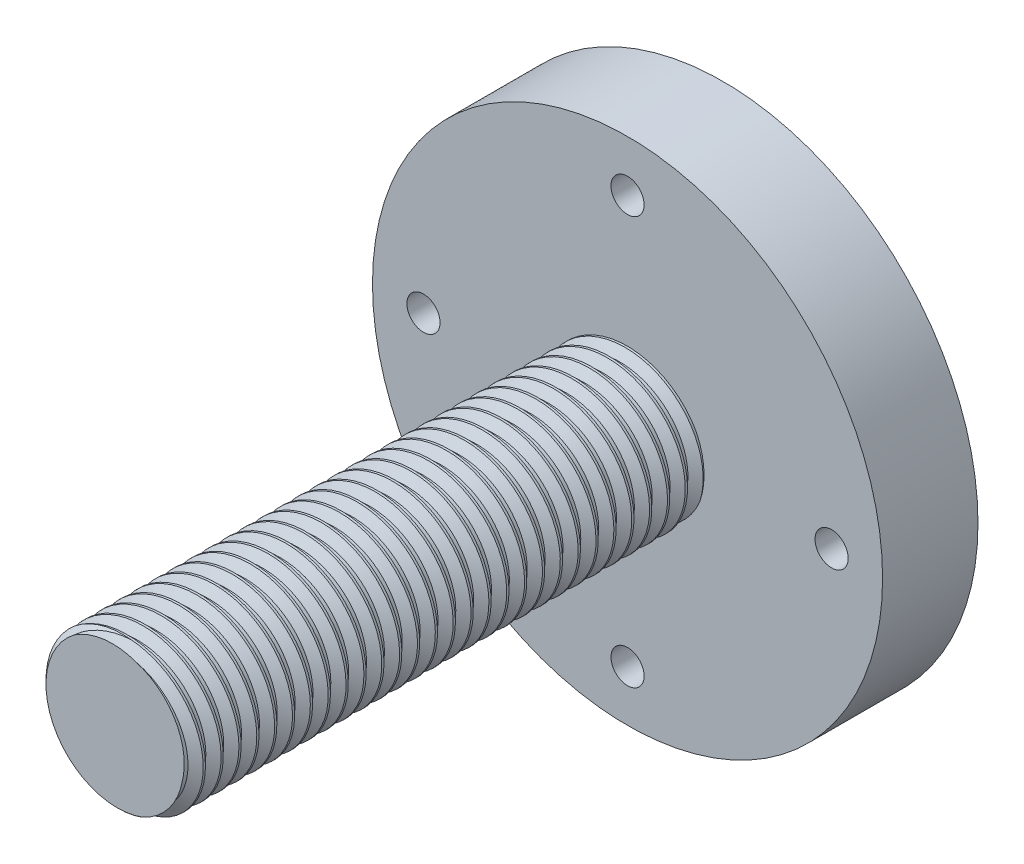
SolidWorks part; units mm, degrees
ref_plane "Front Plane" through (0, 0, 0) normal (0, 0, 1) x (1, 0, 0)
ref_plane "Top Plane" through (0, 0, 0) normal (0, 1, 0) x (1, 0, 0)
ref_plane "Right Plane" through (0, 0, 0) normal (1, 0, 0) x (0, 0, -1)
sketch "Sketch1" plane through (0, 0, 480.4855) normal (0, 0, 1) x (1, 0, 0)
  line L1 (13.2791, -23) -> (26.5581, 0)
  line L2 (26.5581, 0) -> (13.2791, 23)
  line L3 (13.2791, 23) -> (-13.2791, 23)
  line L4 (-13.2791, 23) -> (-26.5581, 0)
  line L5 (-26.5581, 0) -> (-13.2791, -23)
  line L6 (-13.2791, -23) -> (13.2791, -23)
  circle A0 centre (0, 0) radius 23 construction
  dimension "D1" = 46
extrude "Boss-Extrude1" add sketch "Sketch1" along normal blind 18.7
sketch "Sketch2" plane through (0, 0, 499.1855) normal (0, 0, 1) x (1, 0, 0)
  line L0 (-13.2791, 23) -> (-26.5581, 0) construction
  circle A0 centre (0, 0) radius 23
extrude "Cut-Extrude1" cut sketch "Sketch2" against normal through all draft 45 flip side to cut
ref_plane "Plane3" through (0, 0, 489.8355) normal (0, 0, 1) x (1, 0, 0)
mirror "Mirror3" about plane through (0, 0, 489.8355) normal (0, 0, 1) of "Cut-Extrude1"
sketch "Sketch3" plane through (0, 0, 499.1855) normal (0, 0, 1) x (1, 0, 0)
  circle A0 centre (0, 0) radius 15
  dimension "D1" = 30
extrude "Boss-Extrude2" add sketch "Sketch3" along normal blind 100
chamfer "Chamfer1" distance 1 angle 45 1 edges at (15, 0, 599.1855)
thread "Thread1" pitch 3.5 method cut profile "Thread Profile3" start angle 0, offset 11, length 120, pitch 3.5, diameter 30
ref_plane "Plane6" through (-15, 0, 609.1855) normal (0, -1, 0) x (-1, 0, 0)
sketch "Thread Profile3" plane through (-15, 0, 609.1855) normal (0, -1, 0) x (-1, 0, 0)
  line L0 (0, 0) -> (0, 3.5) construction
  line L11 (0, 0) -> (0, 3.0625)
  line L12 (0, 3.0625) -> (-1.8944, 1.9687)
  line L13 (-1.8944, 1.9687) -> (-1.8944, 1.0937)
  line L15 (-1.8944, 1.0937) -> (0, 0)
  line L17 (-1.8944, 1.5312) -> (0, 1.5312) construction
  point P2 (0, 0)
  dimension "Pitch" = 3.5
  dimension "Profile_Angle" = 60
  dimension "Profile_Land" = 0.875
  dimension "Profile_Height" = 1.8944
sketch "Sketch14" plane through (0, 0, 480.4855) normal (0, 0, -1) x (-1, 0, 0)
  line L0 (0, 50) -> (0, -50) construction
  line L1 (50, 0) -> (-50, 0) construction
  line L2 (13.2791, 23) -> (0, 23)
  line L3 (19.9186, 11.5) -> (13.2791, 23)
  line L4 (13.2791, 23) -> (0, 23) construction
  line L5 (19.9186, 11.5) -> (13.2791, 23) construction
  line L6 (26.5581, 0) -> (19.9186, 11.5)
  line L7 (19.9186, -11.5) -> (26.5581, 0)
  line L8 (26.5581, 0) -> (19.9186, 11.5) construction
  line L9 (19.9186, -11.5) -> (26.5581, 0) construction
  line L10 (0, -23) -> (13.2791, -23)
  line L11 (13.2791, -23) -> (19.9186, -11.5)
  line L12 (0, -23) -> (13.2791, -23) construction
  line L13 (13.2791, -23) -> (19.9186, -11.5) construction
  line L14 (-13.2791, -23) -> (0, -23)
  line L15 (-19.9186, -11.5) -> (-13.2791, -23)
  line L16 (-13.2791, -23) -> (0, -23) construction
  line L17 (-19.9186, -11.5) -> (-13.2791, -23) construction
  line L18 (-13.2791, 23) -> (-19.9186, 11.5)
  line L19 (0, 23) -> (-13.2791, 23)
  line L20 (-13.2791, 23) -> (-19.9186, 11.5) construction
  line L21 (0, 23) -> (-13.2791, 23) construction
  circle A0 centre (0, 0) radius 50
  circle A1 centre (0, 0) radius 40 construction
  arc A2 (19.9186, 11.5) -> (0, 23) centre (0, 0) ccw
  arc A3 (19.9186, 11.5) -> (0, 23) centre (0, 0) ccw construction
  arc A4 (19.9186, -11.5) -> (19.9186, 11.5) centre (0, 0) ccw
  arc A5 (19.9186, -11.5) -> (19.9186, 11.5) centre (0, 0) ccw construction
  arc A6 (0, -23) -> (19.9186, -11.5) centre (0, 0) ccw
  arc A7 (0, -23) -> (19.9186, -11.5) centre (0, 0) ccw construction
  arc A8 (-19.9186, -11.5) -> (0, -23) centre (0, 0) ccw
  arc A9 (-19.9186, -11.5) -> (0, -23) centre (0, 0) ccw construction
  arc A10 (0, 23) -> (-19.9186, 11.5) centre (0, 0) ccw
  arc A11 (0, 23) -> (-19.9186, 11.5) centre (0, 0) ccw construction
  circle A12 centre (40, 0) radius 3.25
  circle A13 centre (0, 40) radius 3.25
  circle A14 centre (-40, 0) radius 3.25
  circle A15 centre (0, -40) radius 3.25
  dimension "D1" = 100
  dimension "D7" = 80
  dimension "D11" = 6.5
  dimension "D2" = 0
  dimension "D3" = 0
  dimension "D4" = 0
  dimension "D5" = 0
  dimension "D6" = 0
extrude "Boss-Extrude3" add sketch "Sketch14" against normal up to surface (18.7 mm away) up to face at (13.8418, 0.7754, 499.1855)
